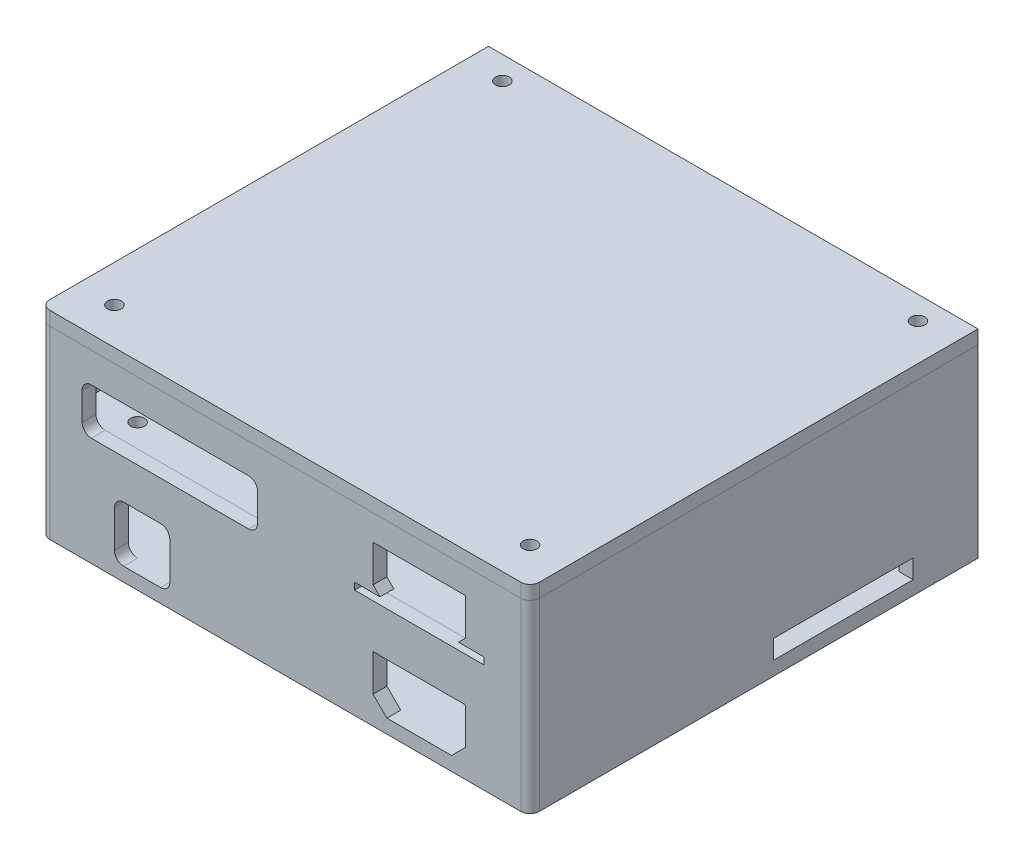
SolidWorks part; units mm, degrees
ref_plane "Front Plane" through (0, 0, 0) normal (0, 0, 1) x (1, 0, 0)
ref_plane "Top Plane" through (0, 0, 0) normal (0, 1, 0) x (1, 0, 0)
ref_plane "Right Plane" through (0, 0, 0) normal (1, 0, 0) x (0, 0, -1)
sketch "Sketch1" plane through (0, 0, 0) normal (0, 1, 0) x (1, 0, 0)
  line L0 (-50, 40) -> (-45, 40) construction
  line L1 (-50, 45) -> (50, 45)
  line L2 (-50, 45) -> (-50, -45) construction
  line L3 (-50, -45) -> (50, -45) construction
  line L4 (50, 45) -> (50, -45) construction
  line L5 (-50, 45) -> (50, -45) construction
  line L6 (-50, -45) -> (50, 45) construction
  line L7 (-45, 40) -> (45, 40) construction
  line L8 (45, 40) -> (50, 40) construction
  line L9 (-45, 40) -> (-45, 25.84) construction
  line L10 (-45, 25.84) -> (-45, 5.84) construction
  line L11 (-45, 15.84) -> (-50, 15.84) construction
  line L12 (0, 45) -> (0, -45) construction
  line L13 (-34, 33) -> (-34, 35) construction
  line L14 (-38, -45) -> (38, -45) construction
  line L15 (-38, -45) -> (-38, 35) construction
  line L16 (-38, 35) -> (38, 35) construction
  line L17 (38, -45) -> (38, 35) construction
  line L18 (-38, -45) -> (38, 35) construction
  line L19 (-38, 35) -> (38, -45) construction
  line L20 (-35.5, 31.5) -> (-38, 31.5) construction
  line L21 (-32.5, 31.5) -> (20, 31.5) construction
  line L22 (-22.5, -36.5) -> (-38, -36.5) construction
  line L23 (-21, -38) -> (-21, -45) construction
  line L24 (34, -25.5) -> (38, -25.5) construction
  line L25 (32.5, -27) -> (32.5, -45) construction
  line L26 (-50, -45) -> (-50, -52) construction
  line L27 (-50, -52) -> (50, -52)
  line L28 (50, -52) -> (50, -45) construction
  line L29 (-50, 45) -> (-53, 45)
  line L30 (-53, 45) -> (-53, -52)
  line L31 (-53, -52) -> (-50, -52)
  line L32 (50, -52) -> (53, -52)
  line L33 (53, -52) -> (53, 45)
  line L34 (53, 45) -> (50, 45)
  circle A0 centre (-45, 40) radius 1.5
  circle A1 centre (45, 40) radius 1.5
  circle A2 centre (-45, 25.84) radius 1.5
  circle A3 centre (-45, 5.84) radius 1.5
  circle A4 centre (45, 5.84) radius 1.5
  circle A5 centre (45, 25.84) radius 1.5
  circle A6 centre (-34, 31.5) radius 1.5
  circle A7 centre (21.5, 31.5) radius 1.5
  circle A8 centre (-21, -36.5) radius 1.5
  circle A9 centre (32.5, -25.5) radius 1.5
  point P0 (0, 0)
  point P24 (0, -5)
  dimension "D4" = 3
  dimension "D8" = 76
  dimension "D10" = 3
  dimension "D13" = 52.5
  dimension "D14" = 15.5
  dimension "D16" = 4
  dimension "D1" = 100
  dimension "D2" = 90
  dimension "D3" = 5
  dimension "D5" = 5
  dimension "D6" = 29.16
  dimension "D7" = 20
  dimension "D9" = 80
  dimension "D11" = 2
  dimension "D12" = 2.5
  dimension "D15" = 7
  dimension "D17" = 18
  dimension "D18" = 7
  dimension "D19" = 3
  dimension "D20" = 3
extrude "Boss-Extrude1" add sketch "Sketch1" along normal blind 3
sketch "Sketch2" plane through (-53, 0, 0) normal (-1, 0, 0) x (0, 0, 1)
  line L0 (-45, 0) -> (-45, 40)
  line L1 (-45, 40) -> (52, 40)
  line L2 (52, 40) -> (52, 0)
  line L3 (52, 0) -> (-45, 0)
  dimension "D1" = 40
extrude "Boss-Extrude2" add sketch "Sketch2" against normal blind 3
sketch "Sketch3" plane through (53, 0, 0) normal (1, 0, 0) x (0, 0, -1)
  line L0 (-52, 40) -> (45, 40)
  line L1 (45, 40) -> (45, 0)
  line L2 (45, 0) -> (-52, 0)
  line L3 (-52, 0) -> (-52, 40)
extrude "Boss-Extrude3" add sketch "Sketch3" against normal blind 3
sketch "Sketch4" plane through (0, 0, 52) normal (0, 0, 1) x (1, 0, 0)
  line L0 (-53, 40) -> (53, 40)
  line L1 (53, 40) -> (53, 0)
  line L2 (53, 0) -> (-53, 0)
  line L3 (-53, 0) -> (53, 0) construction
  line L4 (-53, 0) -> (-53, 40)
extrude "Boss-Extrude4" add sketch "Sketch4" against normal blind 3
sketch "Sketch5" plane through (0, 0, 49) normal (0, 0, -1) x (-1, 0, 0)
  line L0 (25, 3) -> (25, 15)
  line L1 (-50, 40) -> (-50, 3) construction
  line L2 (-50, 3) -> (50, 3) construction
  line L3 (25, 15) -> (37, 15)
  line L5 (37, 15) -> (37, 3)
  line L6 (37, 3) -> (25, 3)
  line L7 (50, 40) -> (50, 3) construction
  line L8 (-39, 14) -> (-39, 3)
  line L10 (-39, 3) -> (-19, 3)
  line L11 (-19, 3) -> (-19, 14)
  line L12 (-19, 14) -> (-39, 14)
  dimension "D1" = 13
  dimension "D2" = 12
  dimension "D3" = 12
  dimension "D4" = 11
  dimension "D5" = 20
  dimension "D6" = 11
extrude "Cut-Extrude1" cut sketch "Sketch5" against normal up to surface (3 mm away) up to face at (0, 20, 52)
fillet "Fillet1" radius 2 4 edges at (-37, 3, 50.5) (-37, 15, 50.5) (-25, 15, 50.5) (-25, 3, 50.5)
chamfer "Chamfer1" distance 3 angle 45 2 edges at (19, 3, 50.5) (39, 3, 50.5)
sketch "Sketch8" plane through (0, 3, 0) normal (0, 1, 0) x (1, 0, 0)
  line L0 (45, 24.34) -> (45, 7.34) construction
  circle A0 centre (45, 25.84) radius 1.5 construction
  circle A1 centre (45, 5.84) radius 1.5 construction
sketch "Sketch7" plane through (0, 0, 0) normal (1, 0, 0) x (0, 0, -1)
  line L0 (30.94, 3) -> (0.74, 3)
  line L1 (0.74, 3) -> (0.74, 7.1)
  line L2 (0.74, 7.1) -> (30.94, 7.1)
  line L3 (30.94, 7.1) -> (30.94, 3)
  line L4 (-52, 3) -> (-49, 3) construction
  line L5 (24.34, 3) -> (7.34, 3) construction
  point P6 (15.84, 3)
  dimension "D1" = 30.2
  dimension "D2" = 4.1
extrude "Cut-Extrude2" cut sketch "Sketch7" against normal through all both and the other way through all
ref_plane "Plane1" through (0, 18, 0) normal (0, 1, 0) x (1, 0, 0)
sketch "Sketch9" plane through (0, 18, 0) normal (0, 1, 0) x (1, 0, 0)
  line L0 (-50, 20.84) -> (-40, 20.84)
  line L1 (50, 45) -> (-50, 45) construction
  line L2 (-40, 20.84) -> (-40, 10.84)
  line L3 (-40, 10.84) -> (-50, 10.84)
  line L4 (-50, -49) -> (-50, 45) construction
  line L5 (-50, 10.84) -> (-50, 20.84)
  line L6 (-50, 20.84) -> (-45, 15.84) construction
  line L7 (-45, 15.84) -> (-40, 10.84) construction
  line L8 (0, 45) -> (0, -2) construction
  line L9 (0, -2) -> (-50, -2) construction
  line L10 (40, 10.84) -> (50, 10.84)
  line L11 (50, 10.84) -> (50, 20.84)
  line L12 (40, 20.84) -> (40, 10.84)
  line L13 (50, 20.84) -> (40, 20.84)
  line L14 (40, -14.84) -> (50, -14.84)
  line L15 (40, -24.84) -> (40, -14.84)
  line L16 (50, -24.84) -> (40, -24.84)
  line L17 (50, -14.84) -> (50, -24.84)
  line L18 (-40, -14.84) -> (-50, -14.84)
  line L19 (-50, -14.84) -> (-50, -24.84)
  line L20 (-40, -24.84) -> (-40, -14.84)
  line L21 (-50, -24.84) -> (-40, -24.84)
  line L22 (-45, 25.84) -> (-45, 5.84) construction
  line L23 (-50, 15.84) -> (-45, 15.84) construction
  circle A0 centre (-45, 15.84) radius 1.5
  circle A2 centre (45, 15.84) radius 1.5
  circle A3 centre (45, -19.84) radius 1.5
  circle A4 centre (-45, -19.84) radius 1.5
  circle A7 centre (-34, 31.5) radius 1.5 construction
  dimension "D1" = 45
extrude "Boss-Extrude5" add sketch "Sketch9" along normal blind 3
chamfer "Chamfer2" distance 10 angle 45 8 edges at (50, 19.5, 14.84) (50, 19.5, -10.84) (-50, 19.5, 14.84) (-50, 19.5, -10.84) (50, 19.5, -20.84) (50, 19.5, 24.84) (-50, 19.5, -20.84) (-50, 19.5, 24.84)
sketch "Sketch10" plane through (0, 21, 0) normal (0, 1, 0) x (1, 0, 0)
  line L0 (-50, 45) -> (50, 45)
  line L1 (50, 45) -> (50, -49)
  line L2 (50, -49) -> (-50, -49)
  line L3 (-50, -49) -> (-50, 45)
  line L4 (-50, -49) -> (-50, 45) construction
  line L5 (-50, -49) -> (-50, 0.74) construction
  line L6 (50, -49) -> (36, -49) construction
  line L7 (50, 0.74) -> (50, -49) construction
  circle A0 centre (-45, 15.84) radius 1.5
  circle A1 centre (-45, -19.84) radius 1.5
  circle A2 centre (45, -19.84) radius 1.5
  circle A3 centre (45, 15.84) radius 1.5
  circle A4 centre (-45, 15.84) radius 1.5 construction
  circle A5 centre (-45, -19.84) radius 1.5 construction
  circle A6 centre (45, -19.84) radius 1.5 construction
  circle A7 centre (45, 15.84) radius 1.5 construction
extrude "Boss-Extrude6" add sketch "Sketch10" along normal blind 2.5 separate body
sketch "Sketch11" plane through (0, 40, 0) normal (0, 1, 0) x (1, 0, 0)
  line L0 (-50, -39) -> (-40, -39)
  line L1 (-50, -49) -> (-50, 45) construction
  line L2 (-40, -39) -> (-40, -49)
  line L3 (50, -49) -> (-50, -49) construction
  line L4 (-40, -49) -> (-50, -49)
  line L5 (-50, -49) -> (-50, -39)
  line L6 (-50, -39) -> (-40, -49) construction
  line L7 (-45, -19.84) -> (-45, -44) construction
  line L8 (0, 0) -> (0, -49) construction
  line L9 (-50, -49) -> (50, -49) construction
  line L10 (45, -19.84) -> (45, -44) construction
  line L11 (50, -39) -> (40, -49) construction
  line L12 (50, -49) -> (50, -39)
  line L13 (40, -49) -> (50, -49)
  line L14 (40, -39) -> (40, -49)
  line L15 (50, -39) -> (40, -39)
  circle A0 centre (-45, -44) radius 1.5
  circle A1 centre (-45, -19.84) radius 1.5 construction
  circle A2 centre (45, -44) radius 1.5
extrude "Boss-Extrude7" add sketch "Sketch11" against normal blind 3
sketch "Sketch12" plane through (0, 0, 49) normal (0, 0, -1) x (-1, 0, 0)
  line L0 (-36, 23.5) -> (-22, 23.5)
  line L1 (-50, 23.5) -> (50, 23.5) construction
  line L2 (-20.5, 25) -> (-19, 26.5)
  line L3 (-19, 26.5) -> (-19, 34.5)
  line L4 (-19, 34.5) -> (-39, 34.5)
  line L5 (-39, 34.5) -> (-39, 26.5)
  line L6 (-39, 26.5) -> (-37.5, 25)
  line L7 (44, 23.5) -> (44, 33.5)
  line L8 (44, 33.5) -> (6, 33.5)
  line L9 (6, 33.5) -> (6, 23.5)
  line L10 (6, 23.5) -> (44, 23.5)
  line L11 (50, 40) -> (50, 3) construction
  line L12 (-39, 14) -> (-39, 6) construction
  line L13 (-19, 14) -> (-39, 14) construction
  line L14 (-29, 23.5) -> (-29, 14) construction
  line L15 (-19, 6) -> (-19, 14) construction
  line L16 (-37.5, 25) -> (-43, 25)
  line L17 (-43, 25) -> (-43, 23.5)
  line L18 (-43, 23.5) -> (-36, 23.5)
  line L19 (-20.5, 25) -> (-15, 25)
  line L20 (-15, 25) -> (-15, 23.5)
  line L21 (-15, 23.5) -> (-22, 23.5)
  line L22 (-37.5, 25) -> (-36, 23.5) construction
  line L23 (-20.5, 25) -> (-22, 23.5) construction
  dimension "D1" = 28
  dimension "D2" = 10
  dimension "D3" = 38
  dimension "D4" = 6
extrude "Cut-Extrude3" cut sketch "Sketch12" against normal up to surface (3 mm away) up to face at (-31, 9, 52)
sketch "Sketch14" plane through (0, 23.5, 0) normal (0, 1, 0) x (1, 0, 0)
  line L0 (29, -52) -> (29, -39) construction
  line L1 (53, -52) -> (-53, -52) construction
  line L2 (18.5, -39) -> (39.5, -39) construction
  line L3 (15, -52) -> (43, -52) construction
  circle A0 centre (18.5, -39) radius 1
  circle A1 centre (39.5, -39) radius 1
  point P7 (29, -39)
  point P11 (29, -52)
  dimension "D3" = 2
  dimension "D1" = 13
  dimension "D2" = 21
extrude "Cut-Extrude4" cut sketch "Sketch14" against normal up to surface (2.5 mm away) up to face at (45, 21, 21.34)
sketch "Sketch15" plane through (0, 23.5, 0) normal (0, 1, 0) x (1, 0, 0)
  line L0 (-40, -44) -> (-10, -44) construction
  line L1 (-25, -44) -> (-25, -52) construction
  line L3 (-44, -52) -> (-6, -52) construction
  line L4 (-50, -49) -> (50, -49) construction
  circle A0 centre (-40, -44) radius 1.5
  circle A1 centre (-10, -44) radius 1.5
  point P10 (-25, -52)
  dimension "D1" = 30
  dimension "D2" = 3
  dimension "D3" = 3
  dimension "D4" = 5
extrude "Cut-Extrude5" cut sketch "Sketch15" against normal up to surface (2.5 mm away) up to face at (39.5, 21, 38)
sketch "Sketch16" plane through (0, 23.5, 0) normal (0, 1, 0) x (1, 0, 0)
  line L0 (0, 0) -> (0, 16) construction
  circle A0 centre (0, 0) radius 1.25
  circle A1 centre (0, 16) radius 1.25
  dimension "D1" = 16
  dimension "D2" = 2.5
extrude "Cut-Extrude6" cut sketch "Sketch16" against normal up to surface (2.5 mm away) up to face at (-40, 21, 42.5)
sketch "Sketch17" plane through (0, 40, 0) normal (0, 1, 0) x (1, 0, 0)
  line L0 (-53, 45) -> (-53, -52)
  line L1 (53, -52) -> (-53, -52) construction
  line L2 (-53, -52) -> (-53, 45) construction
  line L3 (-53, -52) -> (53, -52)
  line L4 (53, -52) -> (53, 45)
  line L5 (53, 45) -> (-53, 45)
  circle A0 centre (-45, -44) radius 1.5
  circle A1 centre (45, 40) radius 1.5
  circle A2 centre (-45, 40) radius 1.5
  circle A3 centre (45, -44) radius 1.5
  circle A4 centre (45, -44) radius 1.5 construction
  circle A5 centre (45, 40) radius 1.5 construction
  circle A6 centre (-45, -44) radius 1.5 construction
  circle A7 centre (-45, 40) radius 1.5 construction
extrude "Boss-Extrude8" add sketch "Sketch17" along normal blind 3 separate body
fillet "Fillet2" radius 2 4 edges at (-6, 23.5, 50.5) (-6, 33.5, 50.5) (-44, 33.5, 50.5) (-44, 23.5, 50.5)
fillet "Fillet3" radius 2 2 edges at (53, 20, 52) (-53, 20, 52)
fillet "Fillet4" radius 2 2 edges at (53, 41.5, 52) (-53, 41.5, 52)
